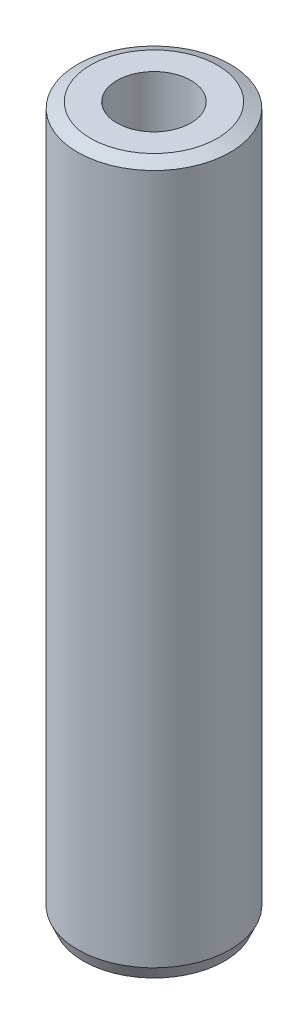
SolidWorks part; units mm, degrees
ref_plane "Front Plane" through (0, 0, 0) normal (0, 0, 1) x (1, 0, 0)
ref_plane "Top Plane" through (0, 0, 0) normal (0, 1, 0) x (1, 0, 0)
ref_plane "Right Plane" through (0, 0, 0) normal (1, 0, 0) x (0, 0, -1)
sketch "Sketch1" plane through (0, 0, 0) normal (0, 1, 0) x (1, 0, 0)
  circle A0 centre (0, 0) radius 7.5
  dimension "SHAFT_OD" = 15
extrude "Boss-Extrude1" add sketch "Sketch1" along normal blind 69.7104
sketch "Sketch2" plane through (0, 0, 0) normal (0, 1, 0) x (1, 0, 0)
  circle A0 centre (0, 0) radius 3.6349
  dimension "BORE_D" = 7.2698
extrude "Cut-Extrude1" cut sketch "Sketch2" along normal through all
chamfer "Chamfer1" distance 0.5584 angle 66.114 2 edges at (0, 69.7104, 7.5) (0, 0, 7.5) first distance on face at (0, 69.7104, 7.5) first distance on face at (0, 0, 3.6349)
